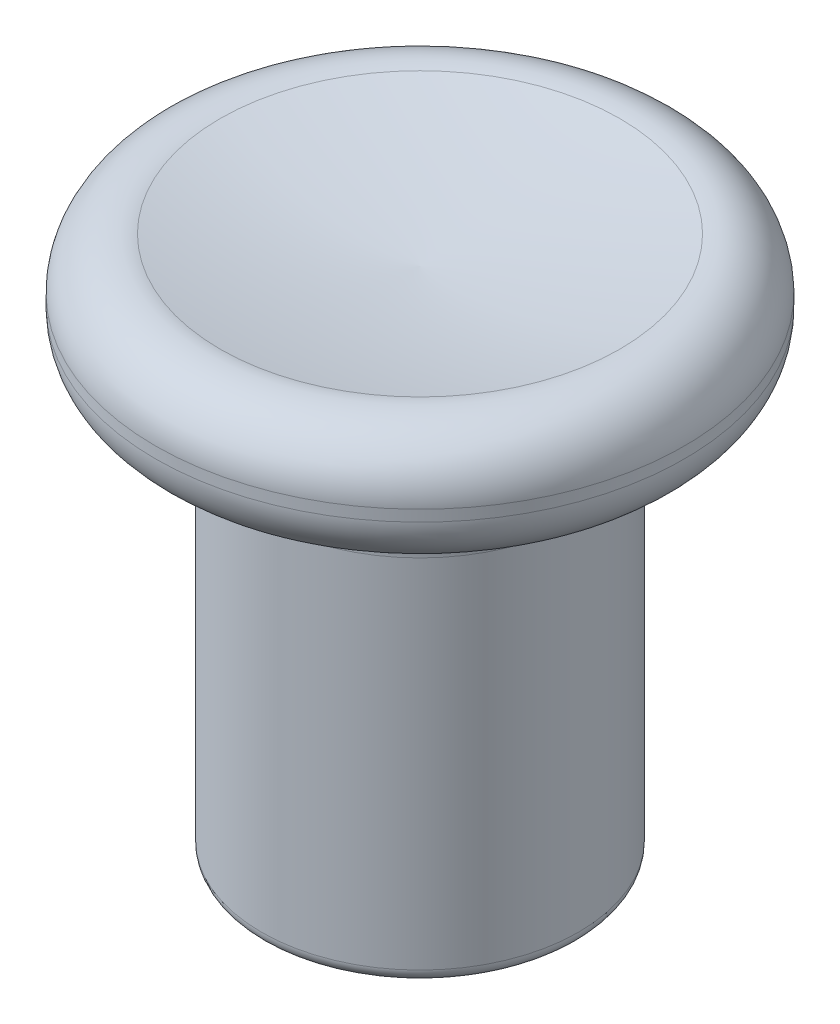
SolidWorks part; units mm, degrees
ref_plane "Front Plane" through (0, 0, 0) normal (0, 0, 1) x (1, 0, 0)
ref_plane "Top Plane" through (0, 0, 0) normal (0, 1, 0) x (1, 0, 0)
ref_plane "Right Plane" through (0, 0, 0) normal (1, 0, 0) x (0, 0, -1)
sketch "草圖1" plane through (0, 0, 0) normal (0, 1, 0) x (1, 0, 0)
  circle A0 centre (0, 0) radius 4.5
  circle A1 centre (0, 0) radius 6
  dimension "D1" = 9
  dimension "D2" = 12
extrude "填料-伸長1" add sketch "草圖1" along normal blind 16
sketch "草圖2" plane through (0, 16, 0) normal (0, 1, 0) x (1, 0, 0)
  circle A0 centre (0, 0) radius 10
  dimension "D1" = 20
extrude "填料-伸長2" add sketch "草圖2" along normal blind 5
sketch "草圖3" plane through (0, 0, 0) normal (1, 0, 0) x (0, 0, -1)
  line L0 (0, 21) -> (0, 19.3163)
  line L1 (10, 21) -> (-10, 21) construction
  line L2 (0, 21) -> (-10, 21)
  spline S0 degree 2 poles (-10, 21) (-5.0903, 19.5961) (0, 19.3163) knots 0 0 0 1 1 1
ref_axis "基準軸1" through (0, 21, 0) along (0, -1, 0)
revolve "除料-旋轉1" cut sketch "草圖3" angle 360 about axis through (0, 21, 0) along (0, -1, 0)
fillet "圓角1" radius 2 3 edges at (0, 21, 10) (0, 16, 10) (0, 16, 6)
fillet "圓角2" radius 0.5 2 edges at (0, 0, 4.5) (0, 0, 6)
